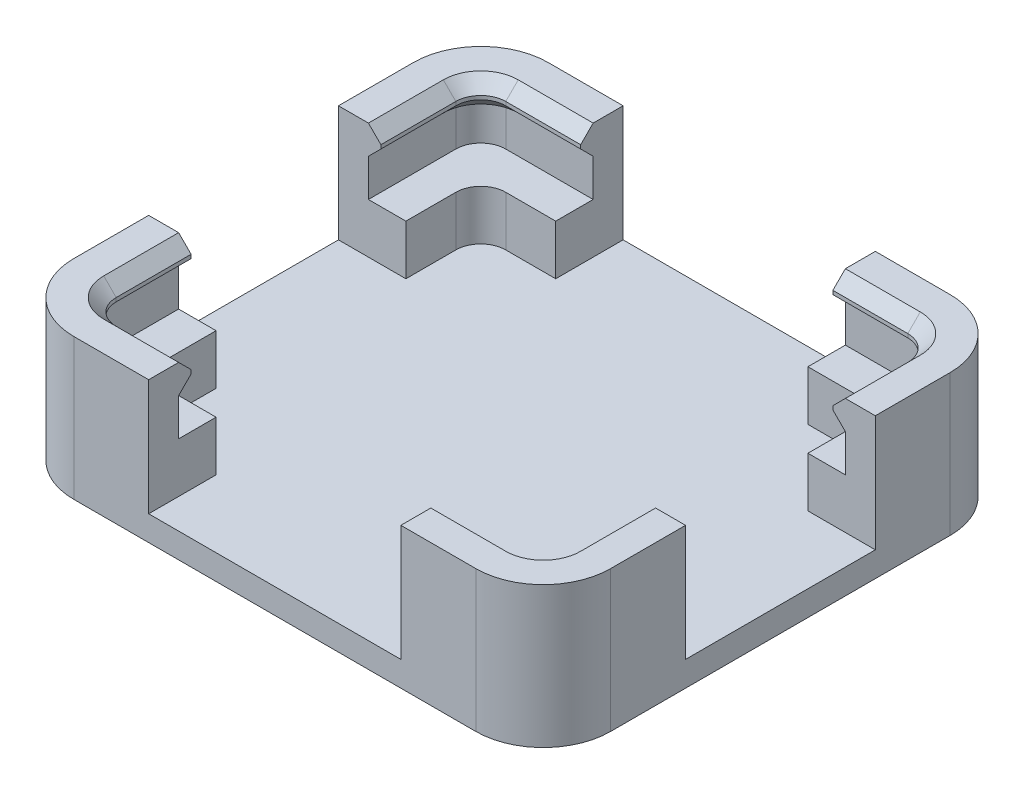
SolidWorks part; units mm, degrees
material "PET"
ref_plane "Front Plane" through (0, 0, 0) normal (0, 0, 1) x (1, 0, 0)
ref_plane "Top Plane" through (0, 0, 0) normal (0, 1, 0) x (1, 0, 0)
ref_plane "Right Plane" through (0, 0, 0) normal (1, 0, 0) x (0, 0, -1)
sketch "Sketch1" plane through (0, 0, 0) normal (0, 1, 0) x (1, 0, 0)
  line L1 (-10.75, -9.5) -> (10.75, -9.5)
  line L2 (-10.75, -9.5) -> (-10.75, 9.5)
  line L3 (-10.75, 9.5) -> (10.75, 9.5)
  line L4 (10.75, -9.5) -> (10.75, 9.5)
  line L5 (0, 9.5) -> (0, -9.5) construction
  line L6 (-10.75, 0) -> (10.75, 0) construction
  point P0 (0, 0)
extrude "Combine Base" add sketch "Sketch1" along normal blind 1
sketch "Sketch4" plane through (0, 1, 0) normal (0, 1, 0) x (1, 0, 0)
  line L0 (-8.05, 3.8) -> (-8.05, 6.8)
  line L5 (-8.05, 6.8) -> (-5.05, 6.8)
  line L6 (-5.05, 6.8) -> (-5.05, 9.5)
  line L31 (10.75, 9.5) -> (-10.75, 9.5) construction
  line L32 (-8.05, 3.8) -> (-10.75, 3.8)
  line L33 (-10.75, 9.5) -> (-10.75, -9.5) construction
  line L34 (5.05, 9.5) -> (5.05, 6.8)
  line L35 (5.05, 6.8) -> (8.05, 6.8)
  line L36 (8.05, 6.8) -> (8.05, 3.8)
  line L37 (8.05, 3.8) -> (10.75, 3.8)
  line L38 (10.75, -9.5) -> (10.75, 9.5) construction
  line L39 (10.75, -3.8) -> (8.05, -3.8)
  line L40 (8.05, -3.8) -> (8.05, -6.8)
  line L41 (8.05, -6.8) -> (5.05, -6.8)
  line L42 (5.05, -6.8) -> (5.05, -9.5)
  line L43 (-10.75, -9.5) -> (10.75, -9.5) construction
  line L44 (-10.75, -3.8) -> (-8.05, -3.8)
  line L45 (-8.05, -3.8) -> (-8.05, -6.8)
  line L46 (-8.05, -6.8) -> (-5.05, -6.8)
  line L47 (-5.05, -6.8) -> (-5.05, -9.5)
  line L49 (-10.75, 9.5) -> (10.75, 9.5)
  line L50 (-10.75, 9.5) -> (-10.75, -9.5)
  line L51 (-10.75, -9.5) -> (10.75, -9.5)
  line L52 (10.75, 9.5) -> (10.75, -9.5)
  line L53 (8.05, -6.8) -> (-8.05, -6.8) construction
  line L54 (8.05, -6.8) -> (8.05, 6.8) construction
  line L55 (8.05, 6.8) -> (-8.05, 6.8) construction
  line L56 (-8.05, -6.8) -> (-8.05, 6.8) construction
  line L57 (0, 6.8) -> (0, -6.8) construction
  line L58 (8.05, 0) -> (-8.05, 0) construction
  point P6 (0, 0)
  line M41 (10.75, -9.5) -> (10.75, 9.5)
  line M42 (10.75, 9.5) -> (-10.75, 9.5)
  line M43 (-10.75, 9.5) -> (-10.75, -9.5)
  line M44 (-10.75, -9.5) -> (10.75, -9.5)
  dimension "D1" = 16.1
  dimension "D2" = 13.6
  dimension "D3" = 3
  dimension "D4" = 2.7
extrude "Stand offs" add sketch "Sketch4" along normal blind 2 contours L32 L0 L5 L6 M42 M43 | L47 L46 L45 L44 M43 M44 | L41 L42 L39 L40 M44 M41 | L36 L37 L34 L35 M41 M42 region at (-8.4172, 1, -7.1672) region at (-8.4172, 1, 7.1672) region at (8.4172, 1, -7.1672) region at (8.4172, 1, 7.1672)
sketch "Sketch5" plane through (0, 3, 0) normal (0, 1, 0) x (1, 0, 0)
  line L0 (-5.05, -9.5) -> (-5.05, -8.3)
  line L1 (-10.75, 9.5) -> (-5.05, 9.5)
  line L2 (-10.75, 9.5) -> (-10.75, 3.8)
  line L3 (-10.75, -9.5) -> (-5.05, -9.5)
  line L4 (10.75, 9.5) -> (10.75, 3.8)
  line L5 (9.55, -8.3) -> (-9.55, -8.3)
  line L6 (9.55, -8.3) -> (9.55, 8.3)
  line L7 (9.55, 8.3) -> (-9.55, 8.3)
  line L8 (-9.55, -8.3) -> (-9.55, 8.3)
  line L9 (0, 8.3) -> (0, -8.3) construction
  line L10 (9.55, 0) -> (-9.55, 0) construction
  line L12 (-5.05, -6.8) -> (-5.05, -9.5) construction
  line L13 (-10.75, -3.8) -> (-9.55, -3.8)
  line L14 (-10.75, -3.8) -> (-8.05, -3.8) construction
  line L15 (-10.75, 3.8) -> (-9.55, 3.8)
  line L16 (-8.05, 3.8) -> (-10.75, 3.8) construction
  line L17 (-5.05, 9.5) -> (-5.05, 8.3)
  line L18 (-5.05, 6.8) -> (-5.05, 9.5) construction
  line L19 (5.05, 9.5) -> (5.05, 8.3)
  line L20 (10.75, 3.8) -> (9.55, 3.8)
  line L21 (8.05, 3.8) -> (10.75, 3.8) construction
  line L22 (10.75, -3.8) -> (9.55, -3.8)
  line L23 (10.75, -3.8) -> (8.05, -3.8) construction
  line L24 (5.05, -9.5) -> (5.05, -8.3)
  line L25 (5.05, -6.8) -> (5.05, -9.5) construction
  line L26 (-10.75, -3.8) -> (-10.75, -9.5)
  line L27 (5.05, 9.5) -> (10.75, 9.5)
  line L28 (10.75, -3.8) -> (10.75, -9.5)
  line L29 (5.05, -9.5) -> (10.75, -9.5)
  point P4 (0, 0)
  line M7 (8.05, 3.8) -> (10.75, 3.8)
  line M8 (10.75, 3.8) -> (10.75, 9.5)
  line M9 (10.75, 9.5) -> (5.05, 9.5)
  line M10 (5.05, 9.5) -> (5.05, 6.8)
  dimension "D1" = 19.1
  dimension "D2" = 16.6
extrude "PCB Containers" add sketch "Sketch5" along normal blind 1.5 contours L17 L1 L2 L15 L8 L7 | L7 L6 M7 M8 M9 M10 | L24 L29 L28 L22 L6 L5 | L13 L26 L3 L0 L5 L8 region at (-7.9, 3, 9.4194) region at (7.3, 3, 8.3806) region at (-10.15, 3, -3.8806) region at (9.6306, 3, -6.05)
sketch "Sketch6" plane through (0, 4.5, 0) normal (0, 1, 0) x (1, 0, 0)
  line L0 (-5.05, 9.5) -> (-10.75, 9.5)
  line L5 (-10.75, 9.5) -> (-10.75, 3.8)
  line L12 (-10.75, 3.8) -> (-9.55, 3.8)
  line L13 (-9.55, 3.8) -> (-9.05, 3.8)
  line L14 (-9.05, 3.8) -> (-9.05, 7.8)
  line L15 (-9.05, 7.8) -> (-5.05, 7.8)
  line L16 (-5.05, 7.8) -> (-5.05, 8.3)
  line L17 (9.55, -3.8) -> (8.05, -3.8) construction
  line L18 (-5.05, 8.3) -> (-5.05, 9.5)
  line L37 (-10.75, -3.8) -> (-9.55, -3.8)
  line L38 (-9.55, -3.8) -> (-9.05, -3.8)
  line L39 (9.55, 8.3) -> (5.05, 8.3) construction
  line L40 (-9.05, -3.8) -> (-9.05, -7.8)
  line L41 (-9.05, -7.8) -> (-5.05, -7.8)
  line L43 (-5.05, -7.8) -> (-5.05, -8.3)
  line L44 (9.05, -7.8) -> (-9.05, -7.8) construction
  line L45 (-5.05, -8.3) -> (-5.05, -9.5)
  line L46 (-5.05, -9.5) -> (-10.75, -9.5)
  line L47 (-10.75, -9.5) -> (-10.75, -3.8)
  line L48 (10.75, -3.8) -> (9.55, -3.8)
  line L49 (9.05, -7.8) -> (9.05, 7.8) construction
  line L50 (9.55, -3.8) -> (9.05, -3.8)
  line L51 (9.05, -3.8) -> (9.05, -7.8)
  line L52 (9.05, -7.8) -> (5.05, -7.8)
  line L53 (9.05, 7.8) -> (-9.05, 7.8) construction
  line L54 (5.05, -7.8) -> (5.05, -8.3)
  line L55 (5.05, -8.3) -> (5.05, -9.5)
  line L56 (5.05, -9.5) -> (10.75, -9.5)
  line L57 (10.75, -9.5) -> (10.75, -3.8)
  line L58 (5.05, 9.5) -> (5.05, 8.3)
  line L59 (-9.05, -7.8) -> (-9.05, 7.8) construction
  line L60 (5.05, 9.5) -> (5.05, 8.3) construction
  line L61 (5.05, 8.3) -> (5.05, 7.8)
  line L62 (5.05, 8.3) -> (5.05, 6.8) construction
  line L63 (5.05, 7.8) -> (9.05, 7.8)
  line L64 (9.05, 7.8) -> (9.05, 3.8)
  line L65 (8.05, 3.8) -> (10.75, 3.8) construction
  line L66 (9.05, 3.8) -> (9.55, 3.8)
  line L67 (9.55, 3.8) -> (10.75, 3.8)
  line L68 (10.75, 3.8) -> (10.75, 9.5)
  line L69 (10.75, 9.5) -> (5.05, 9.5)
  line L70 (0, 7.8) -> (0, -7.8) construction
  line L71 (9.05, 0) -> (-9.05, 0) construction
  point P6 (0, 0)
  point P9 (0, 0)
  line M1 (-5.05, 8.3) -> (-5.05, 9.5)
  line M2 (-5.05, 9.5) -> (-10.75, 9.5)
  line M3 (-10.75, 9.5) -> (-10.75, 3.8)
  line M4 (-10.75, 3.8) -> (-9.55, 3.8)
  line M5 (-9.55, 3.8) -> (-9.55, 8.3)
  line M6 (-9.55, 8.3) -> (-5.05, 8.3)
  dimension "D1" = 0.5
extrude "Snap Ins" add sketch "Sketch6" along normal blind 1.15 contours L41 | L47 L46 L45 L43 L41 L40 L38 L37 | L56 L57 L48 L50 L51 L52 L54 L55 | L68 L69 L58 L61 L63 L64 L66 L67 | M6 M1 M2 M3 M4 M5 | L15 L16 L13 L14 M6 M5 region at (-5.1306, 4.5, -8.9) region at (-5.1136, 4.5, -8.05) region at (-10.15, 4.5, 3.8806) region at (10.6694, 4.5, 6.65) region at (7.9, 4.5, -9.4194)
fillet "Inside Fillets" radius 1 12 edges at (9.55, 3.75, 8.3) (8.05, 2, 6.8) (9.55, 3.75, -8.3) (8.05, 2, -6.8) (-9.05, 5.075, -7.8) (-9.55, 3.75, -8.3) (-8.05, 2, -6.8) (-8.05, 2, 6.8) (-9.55, 3.75, 8.3) (9.05, 5.075, 7.8) (-9.05, 5.075, 7.8) (9.05, 5.075, -7.8)
fillet "Outside Fillets" radius 2.7 4 edges at (-10.75, 2.825, -9.5) (10.75, 2.825, -9.5) (10.75, 2.825, 9.5) (-10.75, 2.825, 9.5)
chamfer "Click in Chamfers" distance 0.5 angle 45 12 edges at (-9.05, 5.65, -5.3) (-6.55, 5.65, -7.8) (-8.7571, 5.65, -7.5071) (6.55, 5.65, -7.8) (9.05, 5.65, -5.3) (8.7571, 5.65, -7.5071) (9.05, 5.65, 5.3) (6.55, 5.65, 7.8) (8.7571, 5.65, 7.5071) (-6.55, 5.65, 7.8) (-9.05, 5.65, 5.3) (-8.7571, 5.65, 7.5071)
chamfer "Pull out Chamfers" distance 0.5 angle 45 12 edges at (-6.55, 4.5, -7.8) (-9.05, 4.5, -5.3) (-8.7571, 4.5, -7.5071) (9.05, 4.5, -5.3) (6.55, 4.5, -7.8) (8.7571, 4.5, -7.5071) (6.55, 4.5, 7.8) (9.05, 4.5, 5.3) (8.7571, 4.5, 7.5071) (-9.05, 4.5, 5.3) (-6.55, 4.5, 7.8) (-8.7571, 4.5, 7.5071)
equation "\"PCB Height\" = 16"
equation "\"PCB Width\" = 18.5"
equation "\"Base Thickness\"= 3'Thickness between PCB and Outer walls"
equation "\"Base Height\"= \"PCB Height\" + \"Base Thickness\"'Height of the mount base"
equation "\"Base Width\"= \"PCB Width\" + \"Base Thickness\"'Width of the mount base"
equation "\"PCB Thickness\"= 2"
equation "\"Tolerance\" = 0.6'Used to add distance between PCB and grippers."
equation "\"Gripper Height\"= \"PCB Height\" + \"Tolerance\"'Final Height in Sketches"
equation "\"Gripper Width\"= \"PCB Width\" + \"Tolerance\"'Final Width in Sketches"
equation "\"D1@Sketch1\"=\"Base Height\""
equation "\"D2@Sketch1\"=\"Base Width\""
equation "\"D1@Sketch4\"=\"Gripper Width\" - \"Base Thickness\""
equation "\"D3@Sketch4\"=\"Base Thickness\""
equation "\"D1@Sketch5\"=\"Gripper Width\""
equation "\"D2@Sketch5\"=\"Gripper Height\""
equation "\"Gripper Thickness\"= \"PCB Thickness\" - 0.5"
equation "\"D1@PCB Containers\" = \"Gripper Thickness\""
equation "\"D1@Snap Ins\" = \"Base Thickness\""
